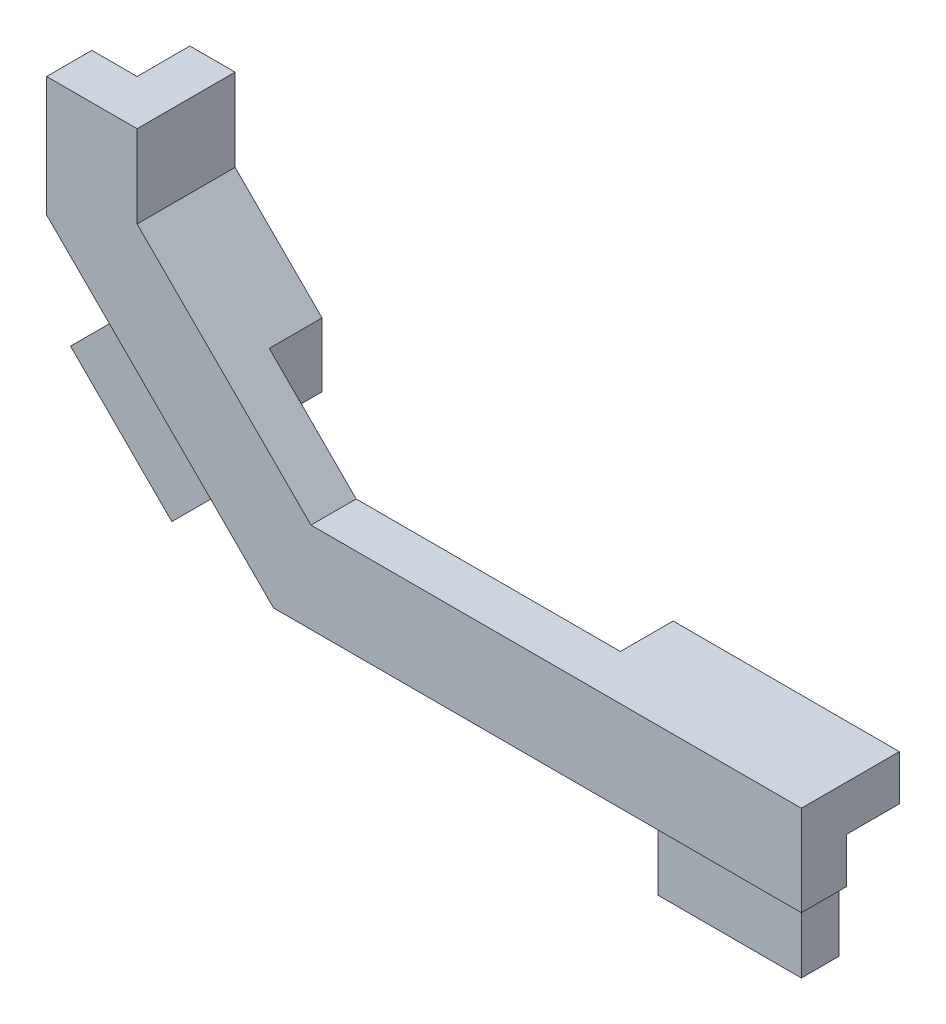
SolidWorks part; units mm, degrees
ref_plane "Front Plane" through (0, 0, 0) normal (0, 0, 1) x (1, 0, 0)
ref_plane "Top Plane" through (0, 0, 0) normal (0, 1, 0) x (1, 0, 0)
ref_plane "Right Plane" through (0, 0, 0) normal (1, 0, 0) x (0, 0, -1)
sketch "Sketch1" plane through (0, 0, 0) normal (0, 1, 0) x (1, 0, 0)
  line L1 (17.5, -1.5) -> (-17.5, -1.5)
  line L2 (17.5, -1.5) -> (17.5, 1.5)
  line L3 (17.5, 1.5) -> (-17.5, 1.5)
  line L4 (-17.5, -1.5) -> (-17.5, 1.5)
  line L5 (17.5, -1.5) -> (-17.5, 1.5) construction
  line L6 (17.5, 1.5) -> (-17.5, -1.5) construction
  point P0 (0, 0)
  dimension "D1" = 35
  dimension "D2" = 3
extrude "Boss-Extrude1" add sketch "Sketch1" along normal blind 6
sketch "Sketch3" plane through (0, 0, -1.5) normal (0, 0, -1) x (-1, 0, 0)
  line L0 (17.5, 0) -> (32.5472, 15.0472)
  line L1 (32.5472, 15.0472) -> (32.5472, 22.9972)
  line L2 (32.5472, 22.9972) -> (26.5472, 22.9972)
  line L3 (26.5472, 22.9972) -> (26.5472, 17.5272)
  line L4 (26.5472, 17.5272) -> (15.02, 6)
  line L7 (-17.5, 0) -> (17.5, 0) construction
  line L8 (-17.5, 6) -> (17.5, 6) construction
  line L9 (15.02, 6) -> (17.5, 6)
  line L10 (17.5, 6) -> (17.5, 0)
  dimension "D1" = 21.28
  dimension "D2" = 6
  dimension "D3" = 7.95
  dimension "D4" = 5.47
  dimension "D5" = 135
extrude "Boss-Extrude2" add sketch "Sketch3" against normal up to surface (3 mm away) up to face at (0, 3, 1.5)
sketch "Sketch4" plane through (0, 0, -1.5) normal (0, 0, -1) x (-1, 0, 0)
  line L0 (-17.5, 6) -> (-17.5, 3)
  line L1 (-17.5, 6) -> (-17.5, 0) construction
  line L2 (-17.5, 6) -> (-2.5, 6)
  line L3 (20.7836, 11.7636) -> (26.5472, 17.5272)
  line L4 (26.5472, 17.5272) -> (26.5472, 22.9972)
  line L5 (26.5472, 22.9972) -> (29.5472, 22.9972)
  line L6 (32.5472, 22.9972) -> (26.5472, 22.9972) construction
  line L7 (29.5472, 22.9972) -> (29.5472, 16.2846)
  line L8 (29.5472, 16.2846) -> (20.7836, 7.521)
  line L9 (-2.5, 3) -> (-17.5, 3)
  line L10 (-2.5, 6) -> (-2.5, 3)
  line L11 (20.7836, 11.7636) -> (20.7836, 7.521)
  dimension "D1" = 3
  dimension "D2" = 15
  dimension "D3" = 4.2426
  dimension "D4" = 5.7636
extrude "Boss-Extrude3" add sketch "Sketch4" along normal blind 3.5
sketch "Sketch5" plane through (0, 0, 0) normal (0, -1, 0) x (1, 0, 0)
  line L1 (7.75, -1.25) -> (17.25, -1.25)
  line L2 (7.75, -1.25) -> (7.75, 1.25)
  line L3 (7.75, 1.25) -> (17.25, 1.25)
  line L4 (17.25, -1.25) -> (17.25, 1.25)
  line L5 (7.75, -1.25) -> (17.25, 1.25) construction
  line L6 (7.75, 1.25) -> (17.25, -1.25) construction
  line L7 (-17.5, 1.5) -> (17.5, 1.5) construction
  line L8 (17.5, 1.5) -> (17.5, -1.5) construction
  line L9 (17.5, -1.5) -> (2.5, -1.5) construction
  point P0 (12.5, 0)
  point P6 (12.5, 0.0853)
  point P8 (12.2127, -0.1786)
  dimension "D1" = 9.5
  dimension "D2" = 0.25
  dimension "D3" = 0.25
  dimension "D4" = 0.25
extrude "Boss-Extrude4" add sketch "Sketch5" along normal blind 4
sketch "Sketch6" plane through (-8.75, -8.75, 0) normal (-0.7071, -0.7071, 0) x (0, 0, 1)
  line L0 (-1.5, 23.0144) -> (1.5, 23.0144) construction
  line L2 (1.5, 33.6544) -> (1.5, 12.3744) construction
  line L3 (-1.5, 12.3744) -> (-1.5, 33.6544) construction
  line L4 (1.25, 18.2644) -> (-1.25, 18.2644)
  line L5 (1.25, 18.2644) -> (1.25, 27.7644)
  line L6 (1.25, 27.7644) -> (-1.25, 27.7644)
  line L7 (-1.25, 18.2644) -> (-1.25, 27.7644)
  line L8 (1.25, 18.2644) -> (-1.25, 27.7644) construction
  line L9 (1.25, 27.7644) -> (-1.25, 18.2644) construction
  point P6 (0, 23.0144)
  dimension "D1" = 9.5
  dimension "D2" = 2.5
extrude "Boss-Extrude5" add sketch "Sketch6" along normal blind 4
